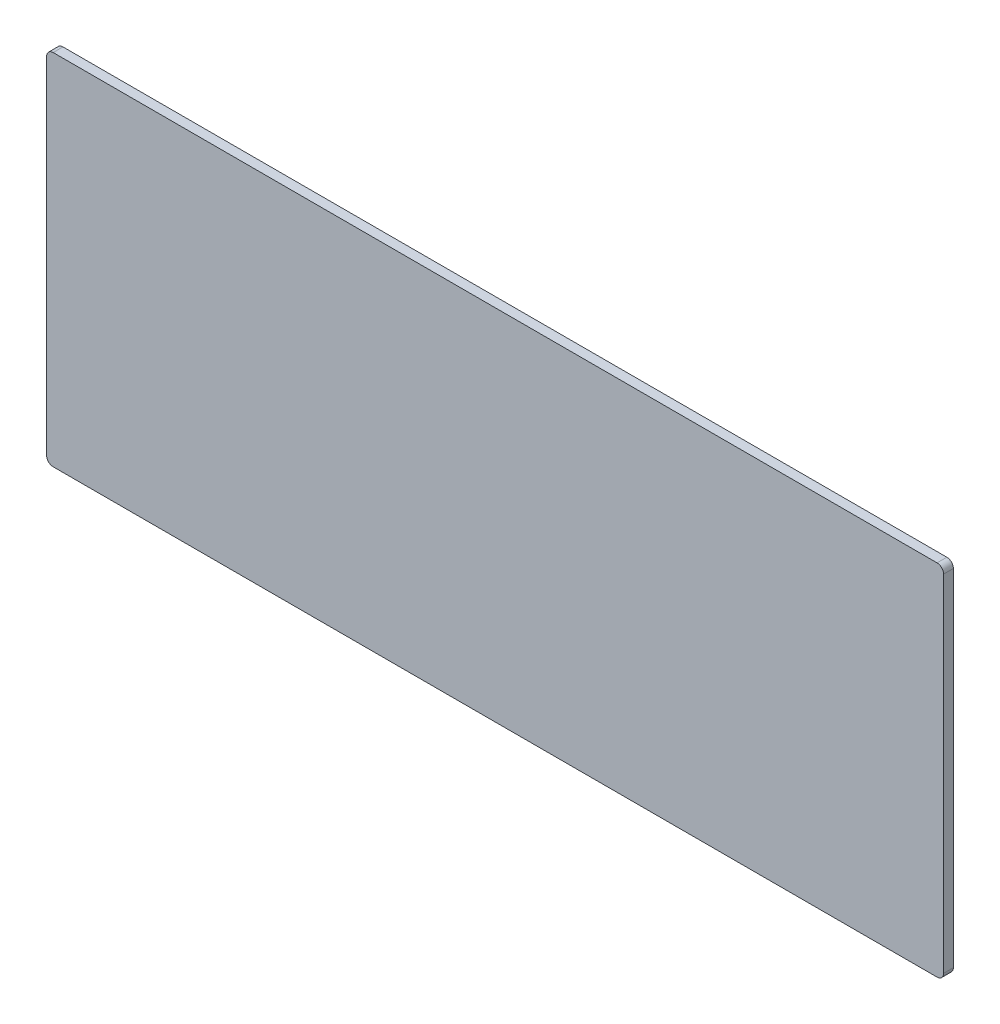
SolidWorks part; units mm, degrees
note: The reader was unsure of these and kept them because the rebuilt part matched: thickness of "Базовая кромка1", "Листовой металл1".
material "Акрил (Средняя-высокая ударопрочность)"
ref_plane "Спереди" through (0, 0, 0) normal (0, 0, 1) x (1, 0, 0)
ref_plane "Сверху" through (0, 0, 0) normal (0, 1, 0) x (1, 0, 0)
ref_plane "Справа" through (0, 0, 0) normal (1, 0, 0) x (0, 0, -1)
sketch "Эскиз1" plane through (0, 0, 0) normal (0, 0, 1) x (1, 0, 0)
  line L1 (-135.5, -37.4961) -> (135.5, -37.4961)
  line L2 (-137.5, -35.4961) -> (-137.5, 70.5039)
  line L3 (-135.5, 72.5039) -> (135.5, 72.5039)
  line L4 (137.5, -35.4961) -> (137.5, 70.5039)
  line L5 (-137.5, -37.4961) -> (137.5, 72.5039) construction
  line L6 (-137.5, 72.5039) -> (137.5, -37.4961) construction
  arc A0 (-137.5, -35.4961) -> (-135.5, -37.4961) centre (-135.5, -35.4961) ccw
  arc A1 (137.5, -35.4961) -> (135.5, -37.4961) centre (135.5, -35.4961) cw
  arc A2 (137.5, 70.5039) -> (135.5, 72.5039) centre (135.5, 70.5039) ccw
  arc A3 (-135.5, 72.5039) -> (-137.5, 70.5039) centre (-135.5, 70.5039) ccw
  point P0 (0, 0)
  dimension "D3" = 2
  dimension "D1" = 275
  dimension "D2" = 110
base flange "Базовая кромка1" sketch "Эскиз1" thickness 3 reverse thickness direction no parameters "D1"=1
sketch "Сгиб-Линии1" [suppressed] plane through (0, 0, 0) normal (0, 1, 0) x (1, 0, 0)
sketch "Граничная рамка1" [suppressed] plane through (0, 0, 0) normal (0, 1, 0) x (1, 0, 0)
sheet metal parameters "Листовой металл1" thickness 3 parameters "D1"=1, "D7"=1
flat pattern "Развертка1" [suppressed]
sketch "Сгиб-Линии2" plane through (0, 0, 0) normal (0, 1, 0) x (1, 0, 0)
sketch3d "Граничная рамка2" [suppressed]
  line L0 (-1.9999, 108.0001, 0) -> (273, 108, 0) construction
  line L1 (-2, -1.9999, 0) -> (272.9999, -2, 0) construction
  line L2 (-1.9999, 108.0001, 0) -> (-2, -1.9999, 0) construction
  line L3 (273, 108, 0) -> (272.9999, -2, 0) construction
